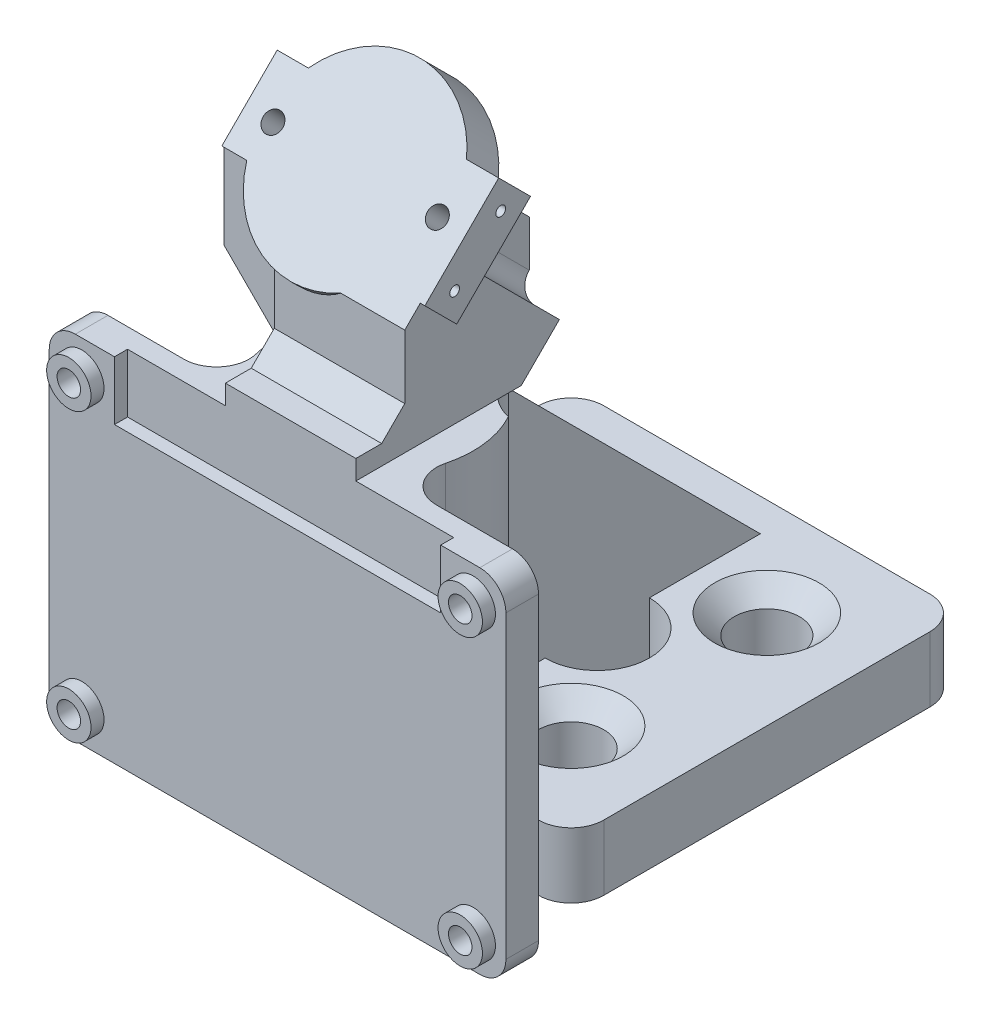
SolidWorks part; units mm, degrees
ref_plane "Front Plane" through (0, 0, 0) normal (0, 0, 1) x (1, 0, 0)
ref_plane "Top Plane" through (0, 0, 0) normal (0, 1, 0) x (1, 0, 0)
ref_plane "Right Plane" through (0, 0, 0) normal (1, 0, 0) x (0, 0, -1)
sketch "Sketch1" plane through (0, 0, 0) normal (0, 1, 0) x (1, 0, 0)
  circle A0 centre (0, 0) radius 15
  dimension "D1" = 30
extrude "Boss-Extrude1" add sketch "Sketch1" along normal blind 54
sketch "Sketch2" plane through (0, 0, 0) normal (1, 0, 0) x (0, 0, -1)
  line L0 (15, 54) -> (-15, 54) construction
  line L1 (-15, 54) -> (20.3553, 54)
  line L2 (-15, 54) -> (-15, 69)
  line L4 (20.3553, 54) -> (20.3553, 69)
  line L5 (-15, 69) -> (2.6777, 86.6777)
  line L6 (2.6777, 86.6777) -> (20.3553, 69)
  point P6 (0, 100)
  dimension "D1" = 25
  dimension "D2" = 15
  dimension "D3" = 15
  dimension "D4" = 45
  dimension "D5" = 15
extrude "Boss-Extrude2" add sketch "Sketch2" along normal mid plane 20
sketch "Sketch4" plane through (0, 42, 42) normal (0, 0.7071, 0.7071) x (1, 0, 0)
  line L0 (10, 38.1838) -> (-10, 38.1838) construction
  line L1 (-12.7, 38.1838) -> (0, 38.1838)
  line L2 (-12.7, 38.1838) -> (-12.7, 63.1838)
  line L3 (-12.7, 63.1838) -> (0, 63.1838)
  line L4 (0, 38.1838) -> (0, 63.1838)
  line L5 (10, 63.1838) -> (-10, 63.1838) construction
  dimension "D1" = 12.7
extrude "Cut-Extrude2" cut sketch "Sketch4" against normal blind 12.7
chamfer "Chamfer1" distance 1 angle 45 1 edges at (-5, 69, 15) first distance on face at (0, 61.5, 15)
sketch "Sketch5" plane through (0, 0, 0) normal (0, -1, 0) x (1, 0, 0)
  circle A0 centre (0, 0) radius 75
  dimension "D1" = 150
sketch "Sketch6" plane through (10, 0, 0) normal (1, 0, 0) x (0, 0, -1)
  line L0 (2.6777, 86.6777) -> (-15, 69) construction
  line L1 (20.3553, 69) -> (2.6777, 86.6777) construction
  line L2 (3.6323, 78.652) -> (-6.9743, 68.0454) construction
  circle A0 centre (3.6323, 78.652) radius 2.6
  circle A1 centre (-6.9743, 68.0454) radius 2.6
  dimension "D4" = 5.2
  dimension "D1" = 6.35
  dimension "D2" = 15
  dimension "D3" = 5
extrude "Cut-Extrude3" [suppressed] cut sketch "Sketch6" against normal through all
sketch "Sketch7" plane through (0, 0, 15) normal (0, 0, 1) x (1, 0, 0)
  line L0 (-31, 0) -> (31, 0)
  line L1 (-35, 4) -> (-35, 50)
  line L2 (-31, 54) -> (31, 54)
  line L3 (35, 4) -> (35, 50)
  line L4 (10, 54) -> (0, 54) construction
  circle A0 centre (-30, 49) radius 1.8
  circle A1 centre (30, 49) radius 1.8
  circle A2 centre (30, 5) radius 1.8
  circle A3 centre (-30, 5) radius 1.8
  arc A4 (31, 54) -> (35, 50) centre (31, 50) cw
  arc A5 (31, 0) -> (35, 4) centre (31, 4) ccw
  arc A6 (-31, 0) -> (-35, 4) centre (-31, 4) cw
  arc A7 (-35, 50) -> (-31, 54) centre (-31, 50) cw
  circle A8 centre (0, 27) radius 5 construction
  point P4 (30, 5)
  point P5 (30, 49)
  point P6 (-30, 49)
  point P7 (-30, 5)
  dimension "D1" = 3.6
  dimension "D2" = 10
  dimension "D3" = 4
  dimension "D4" = 65
  dimension "D5" = 30
  dimension "D6" = 30
  dimension "D7" = 5
  dimension "D8" = 49
  dimension "D9" = 22
  dimension "D10" = 22
  dimension "D11" = 5
extrude "Boss-Extrude4" add sketch "Sketch7" against normal blind 5
fillet "Fillet1" radius 5 2 edges at (-11.1803, 27, 10) (11.1803, 27, 10)
sketch "Sketch8" plane through (0, 0, 0) normal (0, -1, 0) x (1, 0, 0)
  line L1 (30, 0) -> (-30, 0)
  line L2 (30, 0) -> (30, -60)
  line L3 (30, -60) -> (-30, -60)
  line L4 (-30, 0) -> (-30, -60)
  point P4 (0, 0)
  dimension "D1" = 60
  dimension "D2" = 60
extrude "Boss-Extrude5" add sketch "Sketch8" against normal blind 10
sketch "Sketch9" plane through (0, 0, 0) normal (1, 0, 0) x (0, 0, -1)
  line L0 (15, 50) -> (55, 10)
  line L1 (15, 10) -> (15, 54) construction
  line L2 (60, 10) -> (0, 10) construction
  line L3 (15, 50) -> (10, 50)
  line L4 (10, 50) -> (10, 10)
  line L5 (10, 10) -> (55, 10)
  dimension "D1" = 45
  dimension "D2" = 5
  dimension "D3" = 40
extrude "Boss-Extrude6" add sketch "Sketch9" along normal mid plane 8
fillet "Fillet2" radius 5 4 edges at (-30, 5, -60) (30, 5, -60) (-30, 5, 0) (30, 5, 0)
sketch "Sketch10" plane through (0, 10, 0) normal (0, 1, 0) x (1, 0, 0)
  line L0 (-25, 60) -> (25, 60) construction
  line L1 (-15, 45) -> (15, 45) construction
  line L2 (-15, 45) -> (-15, 15) construction
  line L3 (-15, 15) -> (15, 15) construction
  line L4 (15, 45) -> (15, 15) construction
  line L5 (-15, 45) -> (15, 15) construction
  line L6 (-15, 15) -> (15, 45) construction
  circle A0 centre (15, 45) radius 5
  circle A1 centre (-15, 45) radius 5
  circle A2 centre (-15, 15) radius 5
  circle A3 centre (15, 15) radius 5
  point P8 (0, 30)
  dimension "D1" = 10
  dimension "D2" = 30
  dimension "D3" = 30
  dimension "D4" = 30
extrude "Cut-Extrude4" cut sketch "Sketch10" against normal through all
chamfer "Chamfer2" distance 8 angle 45 1 edges at (0, 54, -20.3553)
sketch "Sketch11" plane through (0, 0, 15) normal (0, 0, 1) x (1, 0, 0)
  circle A0 centre (-30, 49) radius 1.8
  circle A1 centre (30, 49) radius 1.8
  circle A2 centre (30, 5) radius 1.8
  circle A3 centre (-30, 5) radius 1.8
  circle A4 centre (-30, 49) radius 1.8 construction
extrude "Extrude-Thin1" add sketch "Sketch11" along normal blind 2 thin thin type one direction wall 1.6
sketch "Sketch12" plane through (0, 0, 15) normal (0, 0, 1) x (1, 0, 0)
  line L0 (-10, 54) -> (-31, 54) construction
  line L1 (-25, 59) -> (25, 59)
  line L2 (-25, 59) -> (-25, 45)
  line L3 (-25, 45) -> (25, 45)
  line L4 (25, 59) -> (25, 45)
  line L5 (-35, 50) -> (-35, 4) construction
  line L6 (35, 4) -> (35, 50) construction
  dimension "D1" = 9
  dimension "D2" = 10
  dimension "D3" = 10
  dimension "D4" = 14
extrude "Cut-Extrude5" cut sketch "Sketch12" against normal blind 2
chamfer "Chamfer3" distance 2 angle 45 1 edges at (0, 59, 13)
sketch "Sketch13" plane through (0, 0, 10) normal (0, 0, -1) x (-1, 0, 0)
  line L649 (-30, 45.8823) -> (-27.3, 47.4412)
  line L650 (-27.3, 47.4412) -> (-27.3, 50.5588)
  line L651 (-27.3, 50.5588) -> (-30, 52.1177)
  line L652 (-30, 52.1177) -> (-32.7, 50.5588)
  line L653 (-32.7, 50.5588) -> (-32.7, 47.4412)
  line L654 (-32.7, 47.4412) -> (-30, 45.8823)
  line L655 (30, 45.8823) -> (32.7, 47.4412)
  line L656 (32.7, 47.4412) -> (32.7, 50.5588)
  line L657 (32.7, 50.5588) -> (30, 52.1177)
  line L658 (30, 52.1177) -> (27.3, 50.5588)
  line L659 (27.3, 50.5588) -> (27.3, 47.4412)
  line L660 (27.3, 47.4412) -> (30, 45.8823)
  line L662 (27.3, 6.5588) -> (27.3, 3.4412)
  line L663 (27.3, 3.4412) -> (30, 1.8823)
  line L664 (30, 1.8823) -> (32.7, 3.4412)
  line L665 (32.7, 3.4412) -> (32.7, 6.5588)
  line L666 (32.7, 6.5588) -> (30, 8.1177)
  line L667 (30, 8.1177) -> (27.3, 6.5588)
  line L668 (-32.7, 6.5588) -> (-32.7, 3.4412)
  line L669 (-32.7, 3.4412) -> (-30, 1.8823)
  line L670 (-30, 1.8823) -> (-27.3, 3.4412)
  line L671 (-27.3, 3.4412) -> (-27.3, 6.5588)
  line L672 (-27.3, 6.5588) -> (-30, 8.1177)
  line L673 (-30, 8.1177) -> (-32.7, 6.5588)
  circle A0 centre (-30, 49) radius 2.7 construction
  circle A1 centre (30, 49) radius 2.7 construction
  circle A2 centre (30, 5) radius 2.7 construction
  circle A3 centre (-30, 5) radius 2.7 construction
  circle A4 centre (-30, 49) radius 1.8 construction
  circle A5 centre (30, 49) radius 1.8 construction
  circle A8 centre (-30, 5) radius 1.8 construction
  circle A9 centre (30, 5) radius 1.8 construction
  dimension "D1" = 5.4
  dimension "D2" = 5.4
  dimension "D3" = 5.4
  dimension "D4" = 5.4
extrude "Cut-Extrude6" cut sketch "Sketch13" against normal blind 2
sketch "Sketch14" plane through (0, 10, 0) normal (0, 1, 0) x (1, 0, 0)
  circle A0 centre (15, 15) radius 8
  circle A1 centre (-15, 15) radius 8
  circle A2 centre (15, 15) radius 5 construction
  dimension "D1" = 16
extrude "Cut-Extrude7" cut sketch "Sketch14" along normal up to surface (44 mm away) up to face at (20.8063, 54, 8.6403)
chamfer "Chamfer4" distance 3 angle 45 4 edges at (-15, 10, -40) (15, 10, -40) (15, 10, -10) (-15, 10, -10)
sketch "Sketch15" plane through (0, 10, 0) normal (0, 1, 0) x (1, 0, 0)
  line L0 (4, 14.4568) -> (4, 55) construction
  line L1 (4, 22) -> (4, 38)
  line L2 (-25, 60) -> (25, 60) construction
  arc A0 (4, 22) -> (4, 38) centre (4, 30) ccw
  dimension "D1" = 8
  dimension "D2" = 30
extrude "Cut-Extrude8" cut sketch "Sketch15" against normal through all
sketch "Sketch16" plane through (0, 42, 42) normal (0, 0.7071, 0.7071) x (1, 0, 0)
  line L1 (10, 63.1838) -> (-10, 63.1838)
  line L2 (10, 63.1838) -> (10, 31.1838)
  line L3 (10, 31.1838) -> (-10, 31.1838)
  line L4 (-10, 63.1838) -> (-10, 31.1838)
  dimension "D1" = 32
extrude "Cut-Extrude9" cut sketch "Sketch16" against normal blind 5.8
sketch "Sketch17" plane through (-10, 0, 0) normal (-1, 0, 0) x (0, 0, 1)
  line L0 (5.4332, 70.3643) -> (0.5542, 65.4853)
  line L1 (10.8988, 64.8988) -> (-6.7789, 82.5765) construction
  line L2 (-11.6579, 77.6974) -> (6.0197, 60.0197) construction
  line L3 (0.5542, 65.4853) -> (9.0395, 57)
  line L4 (9.0395, 57) -> (13, 57)
  line L5 (5.4332, 70.3643) -> (15.8988, 59.8988)
  line L6 (15.8988, 59.8988) -> (13, 57)
  dimension "D1" = 12
extrude "Cut-Extrude10" cut sketch "Sketch17" against normal through all
sketch "Sketch18" plane through (0, 33.0197, 33.0197) normal (0, 0.7071, 0.7071) x (1, 0, 0)
  line L0 (-6.35, 53.1838) -> (-6.35, 63.1838) construction
  line L1 (10, 63.1838) -> (6.7267, 63.1838)
  line L2 (10, 63.1838) -> (10, 53.1838)
  line L3 (10, 53.1838) -> (6.7267, 53.1838)
  line L4 (-22.7, 63.1838) -> (-22.7, 53.1838)
  line L5 (-19.4267, 53.1838) -> (-22.7, 53.1838)
  line L6 (-19.4267, 63.1838) -> (-22.7, 63.1838)
  line L7 (6.7267, 53.1838) -> (-19.4267, 53.1838) construction
  arc A4 (6.7267, 63.1838) -> (-19.4267, 63.1838) centre (-6.35, 58.1838) ccw
  arc A5 (6.7267, 53.1838) -> (-19.4267, 53.1838) centre (-6.35, 58.1838) cw
  point P8 (10, 58.1838)
  point P12 (-6.35, 63.1838)
  point P15 (-6.35, 53.1838)
  dimension "D3" = 14
  dimension "D1" = 5
  dimension "D2" = 32.7
extrude "Boss-Extrude7" add sketch "Sketch18" along normal up to surface (6.9 mm away) up to face at (5, 76.4704, -0.6728)
sketch "Sketch19" plane through (0, 20.8223, 20.8223) normal (0, -0.7071, -0.7071) x (1, 0, 0)
  line L0 (10, -46.9203) -> (10, -58.234) construction
  line L1 (-22.7, -63.1838) -> (-22.7, -53.1838) construction
  line L2 (6.25, -55.1838) -> (10, -55.1838)
  line L3 (3.25, -58.1838) -> (3.25, -63.1838)
  line L4 (6.7267, -63.1838) -> (-10, -63.1838) construction
  line L5 (10, -55.1838) -> (10, -63.1838)
  line L6 (10, -63.1838) -> (3.25, -63.1838)
  arc A0 (6.25, -55.1838) -> (3.25, -58.1838) centre (6.25, -58.1838) ccw
  point P4 (-22.7, -58.1838)
  dimension "D2" = 3
  dimension "D1" = 3.75
extrude "Cut-Extrude11" cut sketch "Sketch19" against normal up to surface (17.2497 mm away) up to face at (-14.0783, 74.6016, -8.5622)
sketch "Sketch20" plane through (0, 33.0197, 33.0197) normal (0, -0.7071, -0.7071) x (1, 0, 0)
  line L0 (6.25, -58.1838) -> (-18.95, -58.1838) construction
  line L1 (-22.7, -63.1838) -> (-22.7, -53.1838) construction
  line L2 (10, -55.1838) -> (10, -63.1838) construction
  circle A0 centre (6.25, -58.1838) radius 1.5
  circle A1 centre (-18.95, -58.1838) radius 1.5
  point P5 (-22.7, -58.1838)
  dimension "D3" = 3
  dimension "D1" = 3.75
  dimension "D2" = 3.75
extrude "Cut-Extrude12" cut sketch "Sketch20" against normal through all
chamfer "Chamfer5" distance 7 angle 45 1 edges at (5.1952, 65.4853, 0.5542)
sketch "Sketch21" plane through (0, 0, 0) normal (0, 0, 1) x (1, 0, 0)
  line L0 (-10, 54) -> (-15, 54)
  line L1 (-15, 54) -> (-23.25, 62.25)
  line L2 (-23.25, 62.25) -> (-23.25, 75.5054)
  line L3 (-23.25, 75.5054) -> (-10, 75.5054)
  line L4 (-10, 54) -> (-10, 75.5054)
  line L5 (-19.4267, 75.5054) -> (-22.7, 75.5054) construction
  point P6 (-10, 75.3713)
  point P8 (-23.8398, 74.8902)
  point P11 (-23.2496, 62.7722)
  point P12 (-23.2218, 62.2218)
  dimension "D1" = 45
  dimension "D2" = 13.25
extrude "Boss-Extrude8" add sketch "Sketch21" against normal blind 5
sketch "Sketch22" plane through (0, 33.0197, 33.0197) normal (0, -0.7071, -0.7071) x (1, 0, 0)
  line L0 (-23.25, -56.9259) -> (-23.25, -47.5529) construction
  line L2 (10, -63.1838) -> (10, -49.1838)
  line L3 (10, -49.1838) -> (10.7, -49.1838)
  line L4 (10.7, -63.1838) -> (10.7, -49.1838)
  line L6 (-22.7, -63.1838) -> (-22.7, -53.1838)
  line L7 (-22.7, -53.1838) -> (-23.25, -53.1838)
  line L8 (-23.25, -63.1838) -> (-23.25, -53.1838)
  line L9 (-19.4267, -63.1838) -> (-22.7, -63.1838) construction
  line L10 (-18.25, -63.1838) -> (-22.7, -63.1838)
  line L11 (-18.25, -63.1838) -> (-18.25, -65.1838)
  line L12 (-18.25, -65.1838) -> (-23.25, -65.1838)
  line L13 (-23.25, -63.1838) -> (-23.25, -65.1838)
  line L15 (10, -63.1838) -> (5.7, -63.1838)
  line L16 (10.7, -63.1838) -> (10.7, -65.1838)
  line L17 (10.7, -65.1838) -> (5.7, -65.1838)
  line L18 (5.7, -63.1838) -> (5.7, -65.1838)
  point P12 (0, 0)
  dimension "D1" = 0.7
  dimension "D2" = 14
  dimension "D3" = 2
  dimension "D4" = 5
extrude "Boss-Extrude9" add sketch "Sketch22" against normal up to surface (6.9 mm away) up to face at (6.25, 80.1016, -4.304)
sketch "Sketch23" plane through (-23.25, 0, 0) normal (-1, 0, 0) x (0, 0, 1)
  line L0 (-8.1931, 83.9907) -> (-13.0721, 79.1116) construction
  line L1 (-5, 62.25) -> (0, 62.25) construction
  line L2 (-11.6579, 77.6974) -> (-6.7789, 82.5765) construction
  line L3 (-5, 71.0395) -> (-13.0721, 79.1116) construction
  line L4 (-18.0219, 84.0614) -> (-13.0721, 79.1116) construction
  line L5 (-8.1931, 83.9907) -> (0.2922, 75.5054) construction
  line L6 (-5, 65.25) -> (0, 65.25) construction
  line L7 (-5, 71.0395) -> (-5, 62.25) construction
  line L8 (0, 75.2132) -> (0, 62.25) construction
  circle A0 centre (-2.5, 65.25) radius 0.75
  circle A1 centre (-9.2184, 80.1369) radius 0.75
  dimension "D3" = 1.5
  dimension "D1" = 2
  dimension "D2" = 3
extrude "Cut-Extrude13" cut sketch "Sketch23" against normal blind 5
sketch "Sketch24" plane through (10.7, 0, 0) normal (1, 0, 0) x (0, 0, -1)
  line L0 (-0.9993, 74.7983) -> (3.8798, 69.9192) construction
  line L1 (13.0721, 79.1116) -> (1.7584, 67.7979) construction
  line L2 (-3.1206, 72.677) -> (8.1931, 83.9907) construction
  line L3 (-3.1206, 72.677) -> (1.7584, 67.7979) construction
  line L4 (6.0718, 81.8693) -> (10.9508, 76.9903) construction
  line L5 (-3.1206, 72.677) -> (8.1931, 83.9907) construction
  line L6 (13.0721, 79.1116) -> (1.7584, 67.7979) construction
  line L7 (8.1931, 83.9907) -> (13.0721, 79.1116) construction
  circle A0 centre (1.4402, 72.3588) radius 0.75
  circle A1 centre (8.5113, 79.4298) radius 0.75
  point P18 (8.4519, 79.3704)
  dimension "D2" = 1.5
  dimension "D1" = 3
  dimension "D3" = 3
extrude "Cut-Extrude14" cut sketch "Sketch24" against normal blind 5
sketch "Sketch25" plane through (0, 0, -20.3553) normal (0, 0, -1) x (-1, 0, 0)
  line L0 (3.375, 62) -> (3.375, 69) construction
  line L1 (-3.25, 62) -> (10, 62) construction
  line L2 (-3.25, 69) -> (10, 69) construction
  circle A0 centre (3.375, 65.5) radius 0.75
  point P8 (3.375, 65.5)
  dimension "D1" = 1.5
extrude "Cut-Extrude15" cut sketch "Sketch25" against normal blind 5
